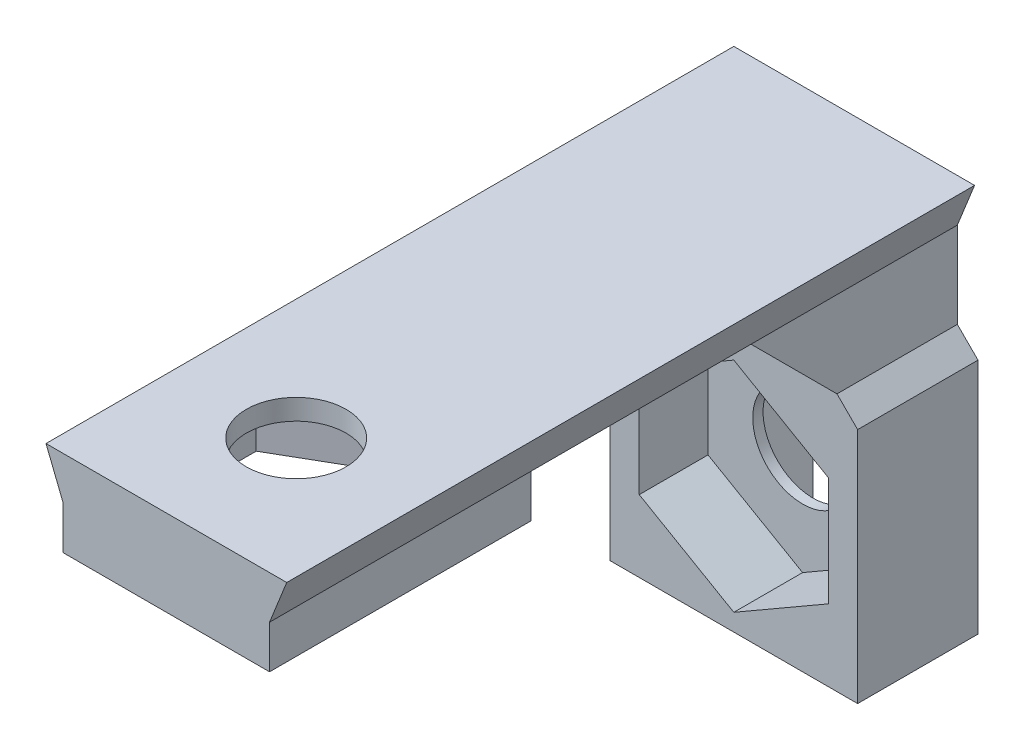
SolidWorks part; units mm, degrees
ref_plane "Front Plane" through (0, 0, 0) normal (0, 0, 1) x (1, 0, 0)
ref_plane "Top Plane" through (0, 0, 0) normal (0, 1, 0) x (1, 0, 0)
ref_plane "Right Plane" through (0, 0, 0) normal (1, 0, 0) x (0, 0, -1)
sketch "Sketch1" plane through (0, 0, 0) normal (0, 1, 0) x (1, 0, 0)
  line L1 (-6, -3.5) -> (6, -3.5)
  line L2 (-6, -3.5) -> (-6, 3.5)
  line L3 (-6, 3.5) -> (6, 3.5)
  line L4 (6, -3.5) -> (6, 3.5)
  line L5 (-6, -3.5) -> (6, 3.5) construction
  line L6 (-6, 3.5) -> (6, -3.5) construction
  point P0 (0, 0)
extrude "Boss-Extrude1" add sketch "Sketch1" along normal blind 20
sketch "Sketch2" plane through (0, 20, 0) normal (0, 1, 0) x (1, 0, 0)
  line L0 (0, 3.5) -> (0, 1.1) construction
  line L1 (6, 3.5) -> (-6, 3.5) construction
  line L22 (0, 3.5) -> (2.4, 3.5)
  line L23 (0, 3.5) -> (-2.4, 3.5)
  line L24 (2.4, 3.5) -> (4.8, 1.1)
  line L25 (0, 1.1) -> (4.8, 1.1)
  line L26 (-2.4, 3.5) -> (-4.8, 1.1)
  line L27 (0, 1.1) -> (-4.8, 1.1)
extrude "Cut-Extrude1" cut sketch "Sketch2" against normal blind 20
sketch "Sketch3" plane through (0, 0, 3.5) normal (0, 0, 1) x (1, 0, 0)
  line L0 (0, 0) -> (0, 7.35) construction
  circle A0 centre (0, 7.35) radius 2.9
extrude "Cut-Extrude2" cut sketch "Sketch3" against normal up to next
sketch "Sketch4" plane through (0, 0, 3.5) normal (0, 0, 1) x (1, 0, 0)
  line L0 (0, 0) -> (0, 7.35) construction
  line L1 (0, 13.7009) -> (-5.5, 10.5254)
  line L2 (-5.5, 10.5254) -> (-5.5, 4.1746)
  line L3 (-5.5, 4.1746) -> (0, 0.9991)
  line L4 (0, 0.9991) -> (5.5, 4.1746)
  line L5 (5.5, 4.1746) -> (5.5, 10.5254)
  line L6 (5.5, 10.5254) -> (0, 13.7009)
  circle A0 centre (0, 7.35) radius 5.5 construction
extrude "Cut-Extrude3" cut sketch "Sketch4" against normal blind 4
sketch "Sketch5" plane through (0, 20, 0) normal (0, 1, 0) x (1, 0, 0)
  line L0 (-6, 3.5) -> (-7, 3.5) construction
  line L1 (6, 3.5) -> (7, 3.5) construction
  line L3 (-7, 3.5) -> (7, 3.5)
  line L4 (-7, 3.5) -> (-7, -36.5)
  line L5 (-7, -36.5) -> (7, -36.5)
  line L6 (7, 3.5) -> (7, -36.5)
extrude "Boss-Extrude2" add sketch "Sketch5" along normal blind 2.5
sketch "Sketch6" plane through (0, 0, -3.5) normal (0, 0, -1) x (-1, 0, 0)
  line L0 (-7, 20) -> (-7, 22.5)
  line L1 (-7, 22.5) -> (-6, 20)
  line L2 (-6, 20) -> (-7, 20)
  line L3 (7, 20) -> (6, 20)
  line L4 (6, 20) -> (7, 22.5)
  line L5 (7, 22.5) -> (7, 20)
extrude "Cut-Extrude4" cut sketch "Sketch6" against normal up to next
sketch "Sketch14" plane through (0, 20, 0) normal (0, -1, 0) x (1, 0, 0)
  line L1 (-6, 21.3) -> (6, 21.3)
  line L2 (-6, 21.3) -> (-6, 36.5)
  line L3 (-6, 36.5) -> (6, 36.5)
  line L4 (6, 21.3) -> (6, 36.5)
  point P7 (0, 0)
extrude "Boss-Extrude6" add sketch "Sketch14" along normal blind 2.5
sketch "Sketch8" plane through (0, 20, 0) normal (0, -1, 0) x (1, 0, 0)
  line L1 (0, 22.5991) -> (5.5, 25.7746)
  line L2 (5.5, 25.7746) -> (5.5, 32.1254)
  line L3 (5.5, 32.1254) -> (0, 35.3009)
  line L4 (0, 35.3009) -> (-5.5, 32.1254)
  line L5 (-5.5, 32.1254) -> (-5.5, 25.7746)
  line L6 (-5.5, 25.7746) -> (0, 22.5991)
  line L7 (0, 36.5) -> (0, 28.95) construction
  line L8 (-6, 36.5) -> (6, 36.5) construction
  circle A0 centre (0, 28.95) radius 5.5 construction
extrude "Cut-Extrude6" cut sketch "Sketch8" against normal blind 1.3 and the other way blind 2.5
sketch "Sketch9" plane through (0, 21.3, 0) normal (0, -1, 0) x (-1, 0, 0)
  circle A0 centre (0, -28.95) radius 2.9
extrude "Cut-Extrude7" cut sketch "Sketch9" against normal up to next
sketch "Sketch10" plane through (0, 0, 0) normal (0, -1, 0) x (1, 0, 0)
  line L1 (-6, 3.5) -> (-7.2, 3.5)
  line L2 (-6, 3.5) -> (-6, -3.5)
  line L3 (-6, -3.5) -> (-7.2, -3.5)
  line L4 (-7.2, 3.5) -> (-7.2, -3.5)
  line L5 (6, 3.5) -> (7.2, 3.5)
  line L6 (6, 3.5) -> (6, -3.5)
  line L7 (6, -3.5) -> (7.2, -3.5)
  line L8 (7.2, 3.5) -> (7.2, -3.5)
extrude "Boss-Extrude3" add sketch "Sketch10" against normal blind 15
chamfer "Chamfer1" distance 1.2 angle 45 2 edges at (7.2, 15, 0) (-7.2, 15, 0)
sketch "Sketch12" plane through (0, 0, 3.5) normal (0, 0, 1) x (1, 0, 0)
  line L1 (-6, 20) -> (6, 20)
  line L2 (-6, 20) -> (-6, 15)
  line L3 (-6, 15) -> (6, 15)
  line L4 (6, 20) -> (6, 15)
extrude "Boss-Extrude5" add sketch "Sketch12" along normal blind 10
chamfer "Chamfer3" distance 10 angle 45 1 edges at (0, 15, 13.5)
